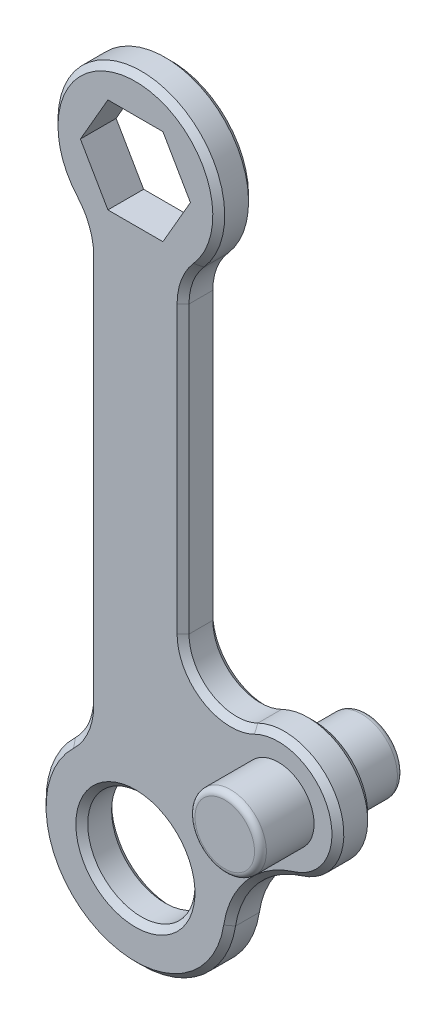
SolidWorks part; units mm, degrees
ref_plane "Płaszczyzna przednia" through (0, 0, 0) normal (0, 0, 1) x (1, 0, 0)
ref_plane "Płaszczyzna górna" through (0, 0, 0) normal (0, 1, 0) x (1, 0, 0)
ref_plane "Płaszczyzna prawa" through (0, 0, 0) normal (1, 0, 0) x (0, 0, -1)
sketch "Sketch1" plane through (0, 0, 0) normal (0, 0, 1) x (1, 0, 0)
  line L0 (0, 50) -> (0, 0) construction
  line L1 (-4, 42.0627) -> (-4, 9.3808)
  line L2 (4, 42.0627) -> (4, 18.0623)
  arc A0 (-5.5385, 5.7728) -> (7.9074, -1.2138) centre (0, 0) ccw
  arc A1 (5.25, 45.3699) -> (-5.25, 45.3699) centre (0, 50) ccw
  arc A2 (13.4672, 5.2201) -> (9.7778, 14.479) centre (12, 10) ccw
  arc A3 (13.4672, 5.2201) -> (7.9074, -1.2138) centre (15.8147, -2.4277) ccw
  arc A4 (9.7778, 14.479) -> (4, 18.0623) centre (8, 18.0623) cw
  arc A5 (-4, 9.3808) -> (-5.5385, 5.7728) centre (-9, 9.3808) cw
  arc A6 (-4, 42.0627) -> (-5.25, 45.3699) centre (-9, 42.0627) ccw
  arc A7 (4, 42.0627) -> (5.25, 45.3699) centre (9, 42.0627) cw
  dimension "D1" = 16
  dimension "D2" = 14
  dimension "D4" = 10
  dimension "D7" = 8
  dimension "D8" = 8
  dimension "D9" = 4
  dimension "D10" = 5
  dimension "D11" = 5
  dimension "D12" = 5
  dimension "D3" = 50
  dimension "D5" = 10
  dimension "D6" = 12
extrude "Boss-Extrude1" add sketch "Sketch1" along normal blind 3 contours A0 A3 A2 A4 L2 A7 A1 A6 L1 A5
sketch "Sketch2" plane through (0, 0, 3) normal (0, 0, 1) x (1, 0, 0)
  line L0 (-4, 42.0627) -> (-4, 9.3808) construction
  line L1 (4.6188, 50) -> (2.3094, 54)
  line L2 (2.3094, 54) -> (-2.3094, 54)
  line L3 (-2.3094, 54) -> (-4.6188, 50)
  line L4 (-4.6188, 50) -> (-2.3094, 46)
  line L5 (-2.3094, 46) -> (2.3094, 46)
  line L6 (2.3094, 46) -> (4.6188, 50)
  circle A0 centre (0, 0) radius 4.5
  circle A1 centre (12, 10) radius 3
  circle A5 centre (0, 50) radius 4 construction
  dimension "D1" = 9
  dimension "D2" = 6
  dimension "D3" = 8
extrude "Cut-Extrude1" cut sketch "Sketch2" against normal blind 3 contours L1 L2 L3 L4 L5 L6 | A0
sketch "Sketch4" plane through (0, 0, 3) normal (0, 0, 1) x (1, 0, 0)
  circle A0 centre (12, 10) radius 3
  dimension "D1" = 6
extrude "Boss-Extrude4" add sketch "Sketch2<5>" along normal blind 4.5 and the other way blind 7.5 separate body contours A1
sketch "Sketch2<5>" plane through (0, 0, 3) normal (0, 0, 1) x (1, 0, 0) same geometry as "Sketch2"
chamfer "Chamfer1" distance 0.5 angle 45 22 edges at (4.3229, 43.8305, 0) (0, 57, 0) (4, 30.0625, 0) (-4.3229, 43.8305, 0) (5.8918, 14.6629, 0) (-4, 25.7218, 0) (16.6448, 11.8508, 0) (-4.4007, 7.4197, 0) (9.7617, 2.803, 0) (-3.6887, -7.0989, 0) (4.3229, 43.8305, 3) (0, 57, 3) (4, 30.0625, 3) (-4.3229, 43.8305, 3) (5.8918, 14.6629, 3) (-4, 25.7218, 3) (16.6448, 11.8508, 3) (-4.4007, 7.4197, 3) (9.7617, 2.803, 3) (-3.6887, -7.0989, 3) (4.5, 0, 0) (4.5, 0, 3)
fillet "Fillet1" radius 0.5 2 edges at (15, 10, -4.5) (15, 10, 7.5)
